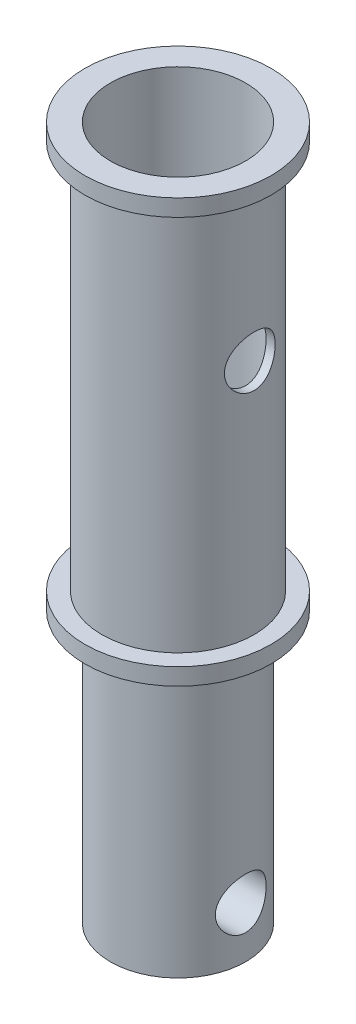
SolidWorks part; units mm, degrees
ref_plane "Front Plane" through (0, 0, 0) normal (0, 0, 1) x (1, 0, 0)
ref_plane "Top Plane" through (0, 0, 0) normal (0, 1, 0) x (1, 0, 0)
ref_plane "Right Plane" through (0, 0, 0) normal (1, 0, 0) x (0, 0, -1)
sketch "Sketch1" plane through (0, 0, 0) normal (0, 1, 0) x (1, 0, 0)
  circle A0 centre (0, 0) radius 4
  circle A1 centre (0, 0) radius 4.5
  circle A2 centre (0, 0) radius 5.5
  dimension "D1" = 8
  dimension "D2" = 11
  dimension "D3" = 9
extrude "Boss-Extrude1" add sketch "Sketch1" along normal blind 1 contours A2 A1 | A1 A0 | A0 region at (0, 0, 0) region at (-4.3727, 0, 0) region at (-5.3444, 0, 0)
extrude "Boss-Extrude2" add sketch "Sketch1<3>" against normal blind 16 contours A0 region at (0, 0, 0)
sketch "Sketch1<3>" plane through (0, 0, 0) normal (0, 1, 0) x (1, 0, 0) same geometry as "Sketch1"
ref_plane "Plane1" through (4, 0, 0) normal (1, 0, 0) x (0, 0, -1)
sketch "Sketch2" plane through (4, 0, 0) normal (1, 0, 0) x (0, 0, -1)
  line L0 (-5.5, 0) -> (5.5, 0) construction
  circle A0 centre (0, -13) radius 1.5
  dimension "D1" = 3
  dimension "D2" = 13
extrude "Cut-Extrude1" cut sketch "Sketch2" against normal blind 13
extrude "Boss-Extrude3" add sketch "Sketch1<4>" along normal blind 25 contours A1 A0 region at (-4.3727, 0, 0)
sketch "Sketch1<4>" plane through (0, 0, 0) normal (0, 1, 0) x (1, 0, 0) same geometry as "Sketch1"
extrude "Boss-Extrude4" add sketch "Sketch1<5>" along normal blind 1 from offset 24 contours A2 A1 region at (-5.3444, 0, 0)
sketch "Sketch1<5>" plane through (0, 0, 0) normal (0, 1, 0) x (1, 0, 0) same geometry as "Sketch1"
sketch "Sketch5" plane through (4, 0, 0) normal (1, 0, 0) x (0, 0, -1)
  line L0 (5.5, 25) -> (-5.5, 25) construction
  circle A0 centre (0, 15) radius 1.5
  dimension "D1" = 3
  dimension "D2" = 10
extrude "Cut-Extrude2" cut sketch "Sketch5" against normal mid plane 23
